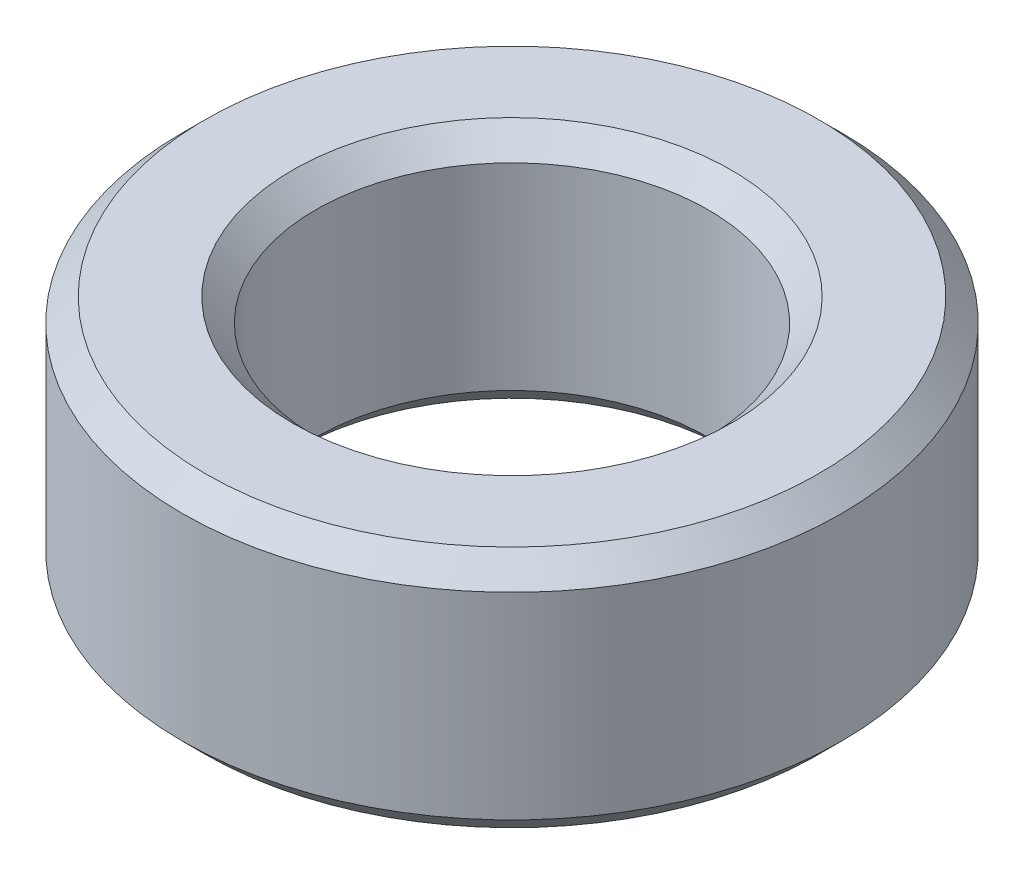
SolidWorks part; units mm, degrees
ref_plane "Front Plane" through (0, 0, 0) normal (0, 0, 1) x (1, 0, 0)
ref_plane "Top Plane" through (0, 0, 0) normal (0, 1, 0) x (1, 0, 0)
ref_plane "Right Plane" through (0, 0, 0) normal (1, 0, 0) x (0, 0, -1)
sketch "Sketch1" plane through (0, 0, 0) normal (0, 1, 0) x (1, 0, 0)
  circle A0 centre (0, 0) radius 32.5
  dimension "SLEEVE_OD" = 65
extrude "Boss-Extrude1" add sketch "Sketch1" along normal blind 23.9602
sketch "Sketch2" plane through (0, 0, 0) normal (0, 1, 0) x (1, 0, 0)
  circle A0 centre (0, 0) radius 19.3548
  dimension "BORE_D" = 38.7096
extrude "Cut-Extrude1" cut sketch "Sketch2" along normal through all
chamfer "Chamfer1" distance 2.2646 angle 45 4 edges at (0, 23.9602, 19.3548) (0, 0, 19.3548) (0, 0, 32.5) (0, 23.9602, 32.5)
